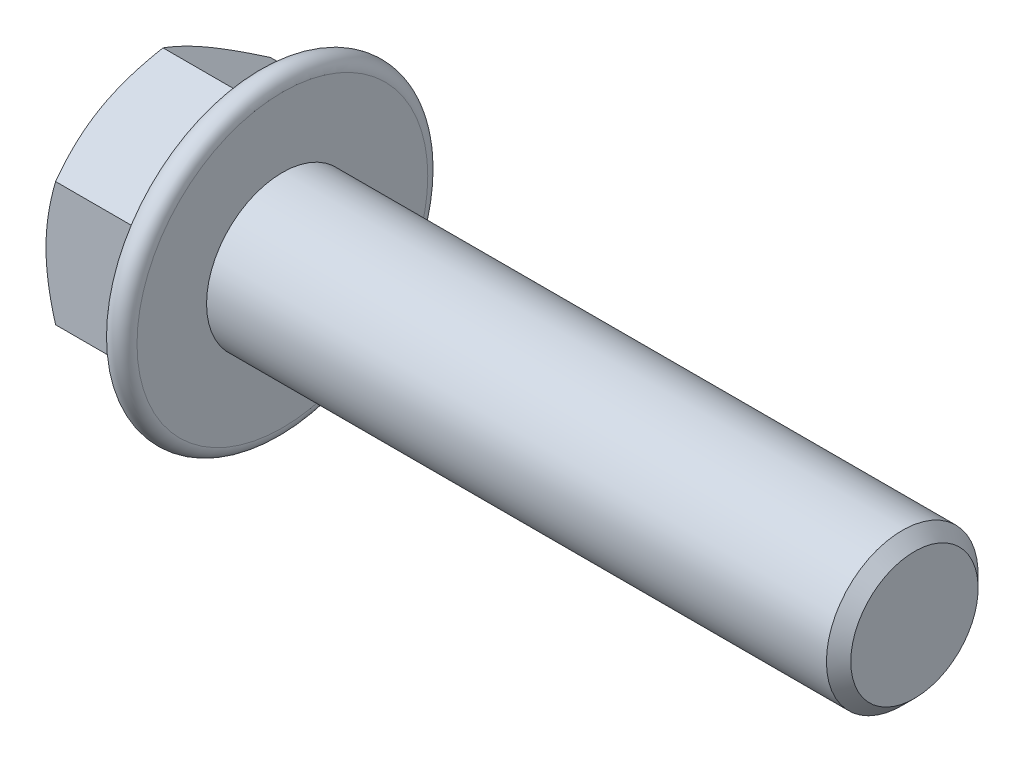
SolidWorks part; units mm, degrees
extrude "BaseHead" add sketch "Sketch1" along normal blind 10.2
sketch "Sketch1" plane through (0, 0, 0) normal (1, 0, 0) x (0, 0, -1)
  line L0 (8.5, 4.9075) -> (8.5, -4.9075)
  line L1 (-8.5, 4.9075) -> (-8.5, -4.9075)
  line L2 (8.5, -4.9075) -> (0, -9.815)
  line L3 (0, -9.815) -> (-8.5, -4.9075)
  line L4 (8.5, 4.9075) -> (0, 9.815)
  line L5 (0, 9.815) -> (-8.5, 4.9075)
  dimension "D2" = 120
  dimension "D3" = 8.5
  dimension "D4" = 8.5
  dimension "D5" = 8.5
ref_plane "Plane1" through (0, 0, 0) normal (0, 0, 1) x (1, 0, 0)
ref_plane "Plane2" through (0, 0, 0) normal (0, 1, 0) x (1, 0, 0)
ref_plane "Plane3" through (0, 0, 0) normal (1, 0, 0) x (0, 0, -1)
sketch "BodySke" plane through (0, 0, 0) normal (0, 0, 1) x (1, 0, 0)
  line L0 (0, 4.9075) -> (0, -4.9075) construction
  line L1 (0, 0) -> (60.2, 0)
  line L2 (0, 0) -> (0, 6)
  line L3 (0, 6) -> (59.236, 6)
  line L4 (60.2, 0) -> (60.2, 5.036)
  line L5 (10.2, 9.815) -> (10.2, 4.9075) construction
  line L6 (60.2, 5.036) -> (59.236, 6)
  line L7 (0, 0) -> (96.52, 0) construction
  line L8 (60.2, -5.036) -> (59.236, -6) construction
  line L9 (0, -6) -> (59.236, -6) construction
  line L10 (11.95, 15.24) -> (11.95, -1.27) construction
  line L11 (30.2, 15.24) -> (30.2, -1.27) construction
  line L12 (10.2, 4.9075) -> (10.2, -4.9075) construction
  dimension "Diameter" = 12
revolve "BaseBody" add sketch "BodySke" angle 360 about L7
cosmetic thread "ThreadCosmetic" [suppressed] parameters "Thread_length"=30, "Thread_minor"=10.072
sketch "Sketch3" plane through (0, 0, 0) normal (0, 0, 1) x (1, 0, 0)
  line L0 (0, 8.5) -> (3.6459, 14.815)
  line L1 (0, 9.815) -> (0, 4.9075) construction
  line L2 (3.6459, 14.815) -> (3.6459, 19.815)
  line L3 (3.6459, 19.815) -> (-10, 19.815)
  line L4 (-10, 19.815) -> (-10, 8.5)
  line L5 (-10, 8.5) -> (0, 8.5)
  line L6 (0, 0) -> (99.06, 0) construction
  line L7 (10.2, 9.815) -> (0, 9.815) construction
  dimension "D1" = 8.5
  dimension "D2" = 5
  dimension "D3" = 10
  dimension "D4" = 5
  dimension "Head_ch_ang" = 30
revolve "HeadChamfer" cut sketch "Sketch3" angle 360 about L6
sketch "Sketch4" plane through (0, 0, 0) normal (0, 0, 1) x (1, 0, 0)
  line L0 (8.1799, 0) -> (8.2, 11.5017)
  line L1 (10.2, 9.815) -> (10.2, 4.9075) construction
  line L2 (8.2, 34.3444) -> (8.2, 16.9779) construction
  line L3 (10.2, 0) -> (10.2, 11.5)
  line L4 (8.3021, 12.5) -> (20.1618, 12.5) construction
  line L5 (0, 0) -> (95.25, 0) construction
  line L6 (0, 0) -> (96.52, 0) construction
  line L7 (8.1799, 0) -> (10.2, 0)
  line L8 (8.3021, -12.5) -> (20.1618, -12.5) construction
  arc A0 (10.2, 11.5) -> (8.2, 11.5017) centre (9.2, 11.5) ccw
  dimension "D1" = 0.1
  dimension "Flange_thickness" = 2
  dimension "Flange_dia" = 25
revolve "Flange" add sketch "Sketch4" angle 360 about L5
fillet "FlangeHexFillet" radius 0.8 6 edges
fillet "HeadFillet" [suppressed] radius 0.8
sketch "ThdSchSke" plane through (0, 0, 0) normal (0, 0, 1) x (1, 0, 0)
  line L0 (30.2, -5.036) -> (29.525, -6)
  line L1 (30.2, -5.036) -> (30.875, -6)
  line L2 (30.875, -6) -> (30.875, -7.5)
  line L3 (-3.175, 0) -> (5.1513, 0) construction
  line L5 (30.875, -7.5) -> (29.525, -7.5)
  line L6 (29.525, -7.5) -> (29.525, -6)
  dimension "Thread_minor" = 10.072
  dimension "Diameter" = 12
  dimension "Start" = 30.2
revolve "ThreadSchematic" [suppressed] cut sketch "ThdSchSke" angle 360 about L3
pattern_linear "ThdSchPat" [suppressed]
equation "\"D3@Sketch1\" = \"Width_flats@Sketch1\" / 2"
equation "\"D4@Sketch1\" = \"D3@Sketch1\""
equation "\"D5@Sketch1\" = \"D4@Sketch1\""
equation "\"Thread_minor@ThreadCosmetic\" = \"Minor_dia@BodySke\""
equation "\"D1@Sketch3\" = \"Width_flats@Sketch1\" / 2"
equation "\"Thread_length@ThreadCosmetic\" = ((sgn( (\"Length@BodySke\" - \"Advance@BodySke\" * 2 ) - \"Thread_nom@BodySke\" )-1)*( (\"Length@BodySke\" - \"Advance@BodySke\" * 2 ) - \"Thread_nom@BodySke\" ))/-2+ \"Thread_nom@BodySke\""
equation "\"Thread_minor@ThdSchSke\" = \"Minor_dia@BodySke\""
equation "\"Diameter@ThdSchSke\" = \"Diameter@BodySke\""
equation "\"Overcut@ThdSchSke\" = \"Diameter@BodySke\" * 1.25"
equation "\"Start@ThdSchSke\" = \"Head_ht@BaseHead\" + \"Length@BodySke\" - \"Thread_length@ThreadCosmetic\"  '---Non-countersunk---"
equation "\"Num_threads@ThdSchPat\" = int( \"Thread_length@ThreadCosmetic\" / \"Advance@BodySke\" + 0.999 )  + 1"
equation "\"Advance@ThdSchPat\" = \"Thread_length@ThreadCosmetic\" /  (\"Num_threads@ThdSchPat\" - 1) 'relax it"
equation "\"Num_threads@ThdSchPat\" = \"Num_threads@ThdSchPat\" - sgn( \"Num_threads@ThdSchPat\" - 1) '---chamfered tips only---"
